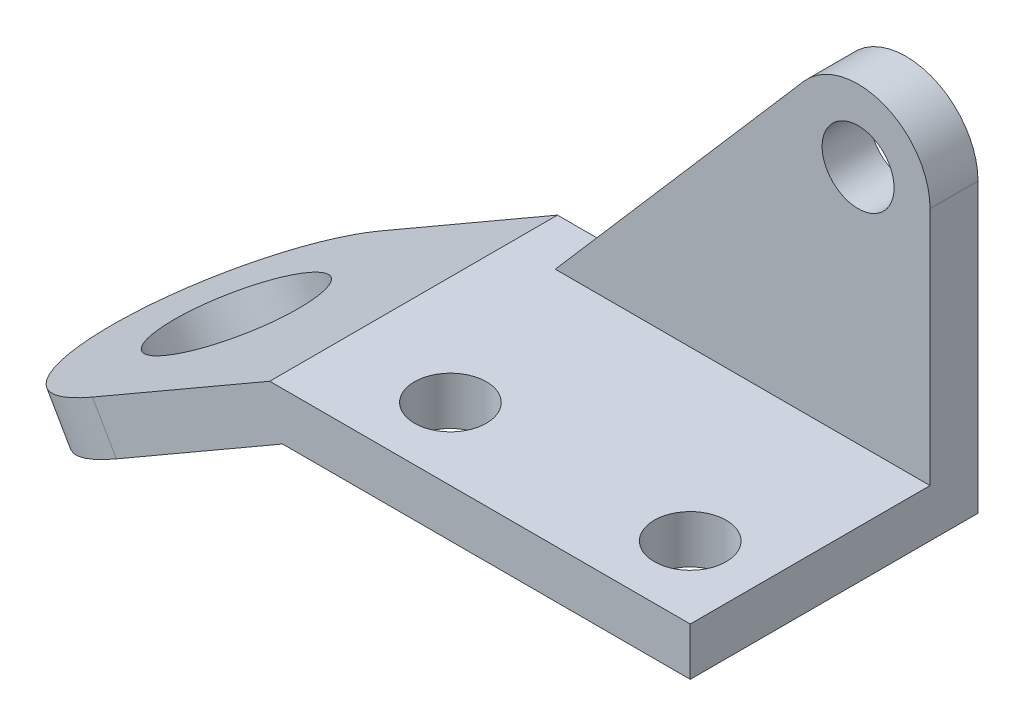
SolidWorks part; units mm, degrees
ref_plane "Front Plane" through (0, 0, 0) normal (0, 0, 1) x (1, 0, 0)
ref_plane "Top Plane" through (0, 0, 0) normal (0, 1, 0) x (1, 0, 0)
ref_plane "Right Plane" through (0, 0, 0) normal (1, 0, 0) x (0, 0, -1)
sketch "Sketch1" plane through (0, 0, 0) normal (0, 0, 1) x (1, 0, 0)
  line L0 (0, 0) -> (85, 0)
  line L1 (0, 0) -> (-60.6218, -35)
  line L2 (-2.6795, 10) -> (85, 10)
  line L3 (-2.6795, 10) -> (-65.6218, -26.3397)
  line L4 (-65.6218, -26.3397) -> (-60.6218, -35)
  line L5 (85, 0) -> (85, 10)
  line L6 (6.8641, 10) -> (58.6603, 69.8189)
  line L7 (85, 60) -> (85, 10)
  circle A0 centre (70, 60) radius 7.5
  arc A1 (85, 60) -> (58.6603, 69.8189) centre (70, 60) ccw
  dimension "D6" = 30
  dimension "D7" = 15
  dimension "D1" = 85
  dimension "D2" = 70
  dimension "D3" = 150
  dimension "D5" = 15
  dimension "D8" = 50
  dimension "D4" = 10
extrude "Boss-Extrude1" add sketch "Sketch1" along normal blind 60 contours L0 L5 L2 L3 L4 L1 region at (-31.0969, -16.1386, 0)
extrude "Boss-Extrude2" add sketch "Sketch1<3>" along normal blind 10 contours L7 A1 L6 L2 A0 region at (56.2209, 34.3774, 0)
sketch "Sketch1<3>" plane through (0, 0, 0) normal (0, 0, 1) x (1, 0, 0) same geometry as "Sketch1"
sketch "Sketch2" plane through (0, 10, 0) normal (0, 1, 0) x (1, 0, 0)
  line L0 (85, -60) -> (85, -10) construction
  line L1 (-2.6795, -60) -> (85, -60) construction
  circle A0 centre (20, -45) radius 7.5
  circle A1 centre (70, -45) radius 7.5
  dimension "D1" = 15
  dimension "D2" = 15
  dimension "D3" = 15
  dimension "D4" = 15
  dimension "D5" = 50
  dimension "D6" = 15
extrude "Cut-Extrude1" cut sketch "Sketch2" against normal through all
sketch "Sketch3" plane through (-5, 8.6603, 0) normal (-0.5, 0.866, 0) x (0.866, 0.5, 0)
  line L0 (-40, 0) -> (-40, -60) construction
  line L1 (2.6795, 0) -> (-70, 0) construction
  line L2 (2.6795, -60) -> (-70, -60) construction
  line L3 (-70, -60) -> (-70, 0) construction
  circle A0 centre (-40, -30) radius 15
  dimension "D2" = 30
  dimension "D1" = 30
fillet "Fillet1" 2 edges at (-63.1218, -30.6699, 0) (-63.1218, -30.6699, 60) type full round first side face at (13.7513, 12.2031, 0) second side face at (6.8462, -6.89, 60) middle face at (-63.1218, -30.6699, 30)
extrude "Cut-Extrude2" cut sketch "Sketch3" against normal through all
